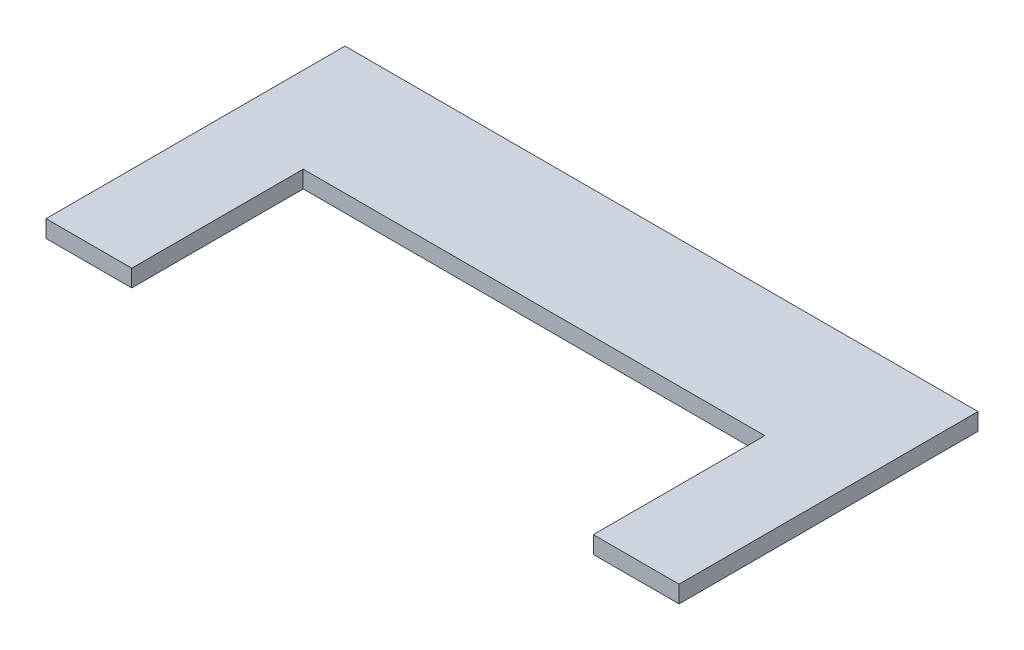
SolidWorks part; units mm, degrees
ref_plane "Front Plane" through (0, 0, 0) normal (0, 0, 1) x (1, 0, 0)
ref_plane "Top Plane" through (0, 0, 0) normal (0, 1, 0) x (1, 0, 0)
ref_plane "Right Plane" through (0, 0, 0) normal (1, 0, 0) x (0, 0, -1)
sketch "Sketch1" plane through (0, 0, 0) normal (0, 1, 0) x (1, 0, 0)
  line L0 (0, 0) -> (0, 52.3) construction
  line L1 (-55.3722, 52.3) -> (55.3722, 52.3)
  line L2 (-55.3722, 52.3) -> (-55.3722, 0)
  line L3 (-55.3722, 0) -> (55.3722, 0) construction
  line L4 (55.3722, 52.3) -> (55.3722, 0)
  line L6 (40.3722, 0) -> (40.3722, 30)
  line L7 (40.3722, 30) -> (-40.3722, 30)
  line L8 (-40.3722, 30) -> (-40.3722, 0)
  line L9 (55.3722, 0) -> (40.3722, 0)
  line L10 (-40.3722, 0) -> (-55.3722, 0)
  dimension "D1" = 15
sketch "Sketch2" plane through (0, 0, 0) normal (1, 0, 0) x (0, 0, -1)
  line L1 (0, 0) -> (52.3, 0)
  line L2 (0, 0) -> (0, 3)
  line L3 (0, 3) -> (52.3, 3)
  line L4 (52.3, 0) -> (52.3, 3)
extrude "Boss-Extrude1" add sketch "Sketch1" along normal up to vertex (3 mm away) up to point (0, 3, -52.3)
